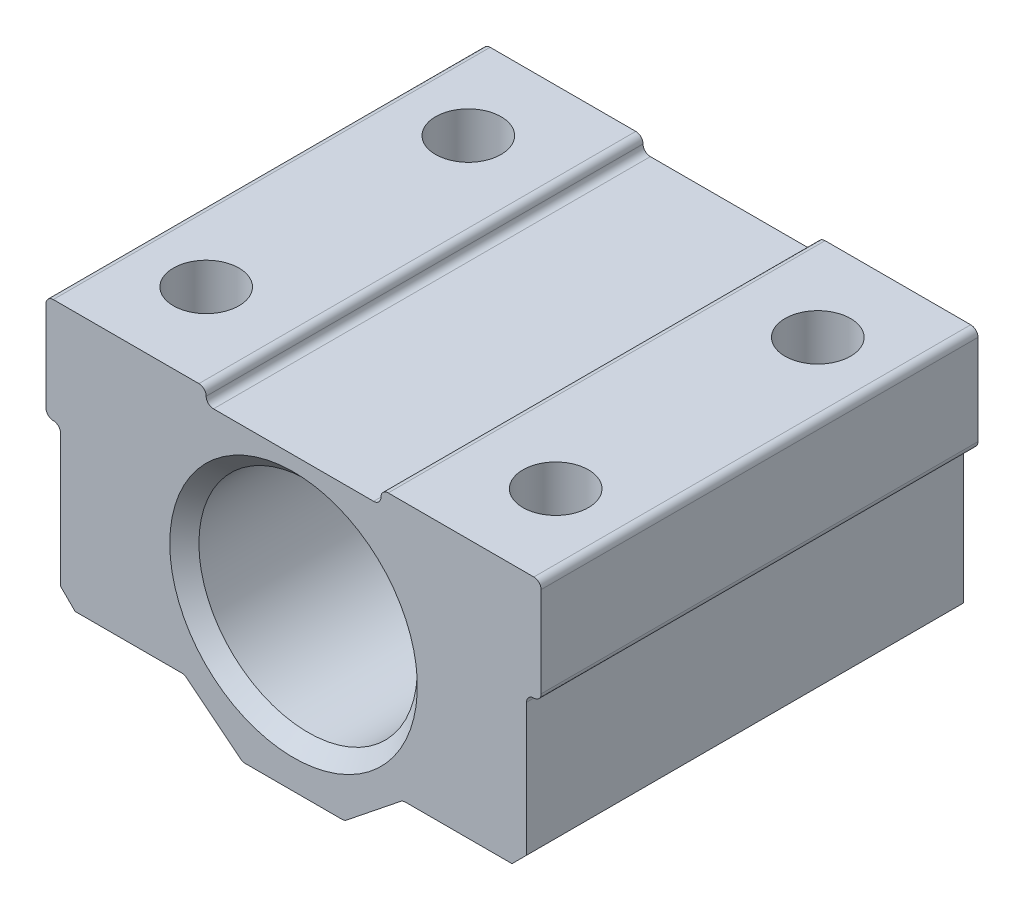
SolidWorks part; units mm, degrees
ref_plane "Piano frontale" through (0, 0, 0) normal (0, 0, 1) x (1, 0, 0)
ref_plane "Piano superiore" through (0, 0, 0) normal (0, 1, 0) x (1, 0, 0)
ref_plane "Piano destro" through (0, 0, 0) normal (1, 0, 0) x (0, 0, -1)
sketch "Schizzo2" plane through (0, 0, 0) normal (0, 0, 1) x (1, 0, 0)
  line L0 (0, 0) -> (11, 0)
  line L1 (34, 0) -> (34, -7.2)
  line L2 (34, -7.2) -> (33, -7.2)
  line L3 (33, -7.2) -> (33, -17.8)
  line L4 (33, -17.8) -> (24.5, -17.8)
  line L5 (1, -17.8) -> (1, -7.2)
  line L6 (1, -7.2) -> (0, -7.2)
  line L7 (0, -7.2) -> (0, 0)
  line L8 (17, 13.7067) -> (17, -26.6004) construction
  line L9 (11, -1) -> (23, -1)
  line L10 (11, 0) -> (11, -1)
  line L11 (23, 0) -> (23, -1)
  line L12 (11, 13.7067) -> (11, -30.861) construction
  line L13 (23, 0) -> (34, 0)
  line L14 (0, -1) -> (34, -1) construction
  line L15 (13.5, -21) -> (20.5, -21)
  line L16 (0, 0) -> (34, 0) construction
  line L17 (9.5, -14.9665) -> (9.5, -25.2087) construction
  line L18 (24.5, -14.9665) -> (24.5, -25.2087) construction
  line L19 (13.5, -21) -> (9.5, -17.8)
  line L20 (20.5, -21) -> (24.5, -17.8)
  line L21 (9.5, -17.8) -> (1, -17.8)
  line L22 (17, 13.7067) -> (17, -30.861) construction
  point P22 (17, -21)
  dimension "D1" = 34
  dimension "D2" = 7.2
  dimension "D3" = 1
  dimension "D4" = 10.6
  dimension "D5" = 32
  dimension "D10" = 3.2
  dimension "D9" = 3.5
  dimension "D11" = 7.5
  dimension "D12" = 7.5
  dimension "D6" = 1
  dimension "D7" = 6
  dimension "D8" = 12
extrude "Estrusione-Estrusione1" add sketch "Schizzo2" against normal blind 30
sketch "Schizzo3" plane through (0, 0, 0) normal (0, 0, 1) x (1, 0, 0)
  line L0 (0, 0) -> (42.7296, 0) construction
  line L1 (0, -21) -> (42.7296, -21) construction
  line L2 (0, 10.0831) -> (0, -34.3108) construction
  line L3 (17, 10.0831) -> (17, -34.3108)
  line L4 (0, -10.5) -> (42.7296, -10.5)
  circle A0 centre (17, -10.5) radius 7.5
  point P13 (17, -10.5)
extrude "Taglio-Estrusione2" cut sketch "Schizzo3" against normal through all contours A0
chamfer "Smusso1" distance 1 angle 45 4 edges at (33, -17.8, -15) (24.5, -10.5, 0) (24.5, -10.5, -30) (1, -17.8, -15)
ref_plane "Piano1" through (0, 0, 0) normal (0, 1, 0) x (1, 0, 0)
fillet "Raccordo1" radius 0.5 14 edges at (9.5, -17.8, -15) (24.5, -17.8, -15) (20.5, -21, -15) (13.5, -21, -15) (1, -7.2, -15) (0, -7.2, -15) (0, 0, -15) (23, -1, -15) (11, -1, -15) (11, 0, -15) (23, 0, -15) (34, 0, -15) (34, -7.2, -15) (33, -7.2, -15)
hole_wizard "Foro per Vite M4-1" positions "Schizzo5" profile "Schizzo4" hole size "M4" standard "Ansi Metric" end condition through all
sketch "Schizzo5" plane through (0, 0, 0) normal (0, 1, 0) x (1, 0, 0)
  line L0 (41.1923, 15) -> (-3.923, 15) construction
  line L2 (17, 40.1827) -> (17, -15.9337) construction
  line L4 (33.5, 0) -> (33.5, 30) construction
  line L5 (0.5, 30) -> (0.5, 0) construction
  line L6 (33.5, 0) -> (23.5, 0) construction
  line L7 (22.5, 30) -> (11.5, 30) construction
  point P0 (29, 24)
  point P2 (29, 6)
  point P4 (5, 6)
  point P6 (5, 24)
  dimension "D1" = 9
  dimension "D2" = 12
sketch "Schizzo4" plane through (29, 0, -24) normal (1, 0, 0) x (0, 0, 1)
  line L0 (0, 0) -> (0, 21)
  line L1 (0, 21) -> (2.25, 21)
  line L2 (2.25, 21) -> (2.25, 0)
  line L5 (2.25, 0) -> (0, 0)
  line L11 (0, -6.35) -> (0, 107.95) construction
  dimension "Thru Hole Dia." = 4.5
  dimension "Thru Hole Depth" = 21
